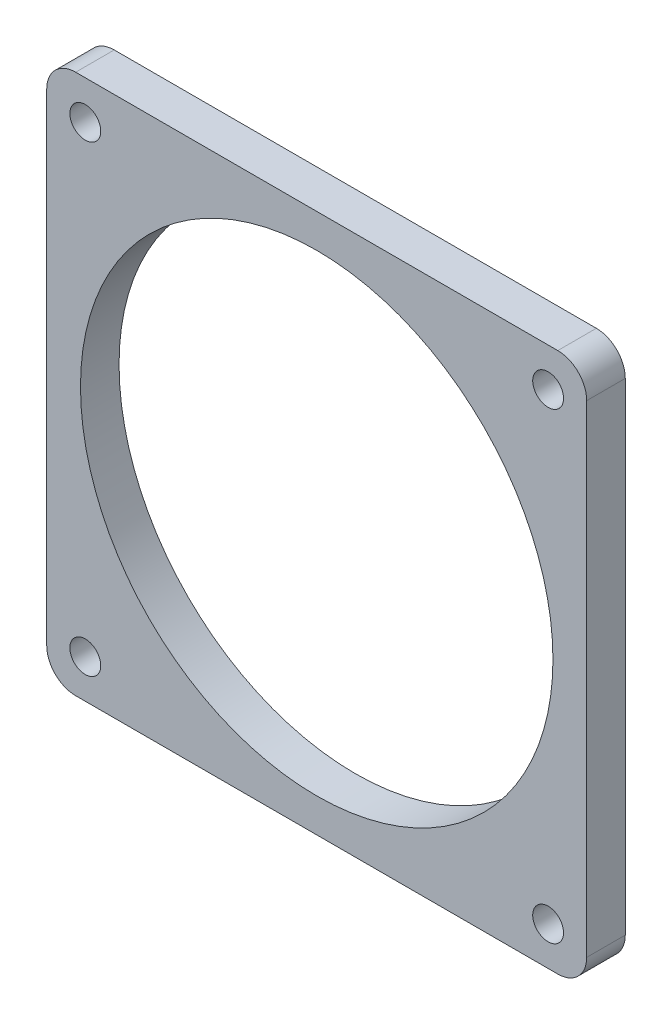
SolidWorks part; units mm, degrees
note: The reader was unsure of these and kept them because the rebuilt part matched: thickness of "Базовая кромка1", "Листовой металл3", "Листовой металл4".
ref_plane "Спереди" through (0, 0, 0) normal (0, 0, 1) x (1, 0, 0)
ref_plane "Сверху" through (0, 0, 0) normal (0, 1, 0) x (1, 0, 0)
ref_plane "Справа" through (0, 0, 0) normal (1, 0, 0) x (0, 0, -1)
other "Configuration Table"
sketch "Эскиз1" plane through (0, 0, 0) normal (0, 0, 1) x (1, 0, 0)
  line L1 (-28, 28) -> (28, 28)
  line L2 (-28, 28) -> (-28, -28)
  line L3 (-28, -28) -> (28, -28)
  line L4 (28, 28) -> (28, -28)
  line L5 (-28, 28) -> (28, -28) construction
  line L6 (-28, -28) -> (28, 28) construction
  point P0 (0, 0)
  dimension "D1" = 56
  dimension "D2" = 56
base flange "Базовая кромка1" sketch "Эскиз1" thickness 4 reverse thickness direction no parameters "D1"=4
sketch "Эскиз6" plane through (0, 0, 0) normal (0, 0, 1) x (1, 0, 0)
  line L0 (-28, -28) -> (28, 28) construction
  circle A0 centre (0, 0) radius 24.5
  circle A1 centre (-24, 24) radius 1.6
  circle A2 centre (24, 24) radius 1.6
  circle A3 centre (24, -24) radius 1.6
  circle A4 centre (-24, -24) radius 1.6
  dimension "D1" = 49
  dimension "D4" = 3.2
  dimension "D2" = 24
  dimension "D3" = 24
  dimension "D7" = 24
  dimension "D8" = 24
  dimension "D5" = 2
  dimension "D6" = 2
extrude "Вырез-Вытянуть1" cut sketch "Эскиз6" against normal blind 4 normal cut yes
fillet "Скругление1" radius 3 4 edges at (-28, 28, -2) (-28, -28, -2) (28, 28, -2) (28, -28, -2)
sketch "Сгиб-Линии1" [suppressed] plane through (0, 0, 0) normal (0, 1, 0) x (1, 0, 0)
sketch "Граничная рамка1" [suppressed] plane through (0, 0, 0) normal (0, 1, 0) x (1, 0, 0)
sheet metal parameters "Листовой металл3" thickness 4 parameters "D1"=3, "D7"=2
flat pattern "Развертка3" [suppressed]
sketch "Сгиб-Линии2" plane through (0, 0, 0) normal (0, 1, 0) x (1, 0, 0)
sketch "Граничная рамка2" [suppressed] plane through (0, 0, 0) normal (0, 1, 0) x (1, 0, 0)
sheet metal parameters "Листовой металл4" thickness 4 parameters "D1"=3, "D7"=2
flat pattern "Развертка3"
sketch "Сгиб-Линии2" plane through (0, 0, 0) normal (0, 1, 0) x (1, 0, 0)
sketch3d "Граничная рамка2" [suppressed]
  line L0 (28, -28, 0) -> (28, 28, 0) construction
  line L1 (-28, -28, 0) -> (-28, 28, 0) construction
  line L2 (28, -28, 0) -> (-28, -28, 0) construction
  line L3 (28, 28, 0) -> (-28, 28, 0) construction
